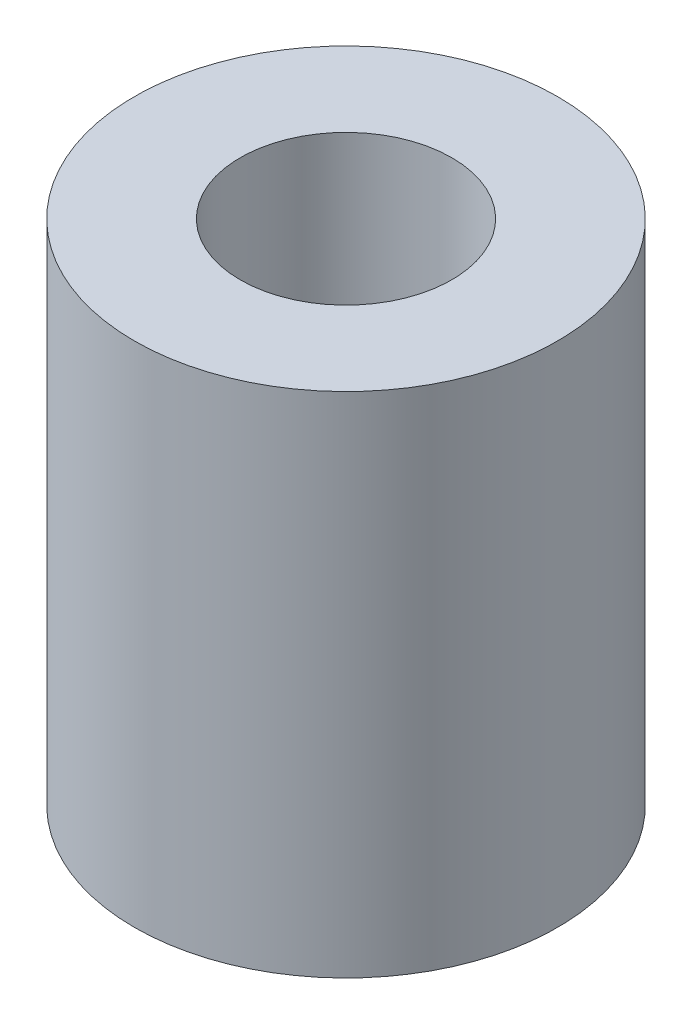
SolidWorks part; units mm, degrees
material "Brass"
ref_plane "Front Plane" through (0, 0, 0) normal (0, 0, 1) x (1, 0, 0)
ref_plane "Top Plane" through (0, 0, 0) normal (0, 1, 0) x (1, 0, 0)
ref_plane "Right Plane" through (0, 0, 0) normal (1, 0, 0) x (0, 0, -1)
sketch "Sketch1" plane through (0, 0, 0) normal (0, 1, 0) x (1, 0, 0)
  circle A0 centre (0, 0) radius 2.5
  dimension "D1" = 5
extrude "Boss-Extrude1" add sketch "Sketch1" along normal blind 6
hole_wizard "M3x0.5 Tapped Hole1" positions "Sketch2" profile "Sketch3" tap size "M3x0.5" standard "ANSI Metric" end condition through all
sketch "Sketch2" plane through (0, 6, 0) normal (0, 1, 0) x (1, 0, 0)
  point P0 (0, 0)
sketch "Sketch3" plane through (0, 6, 0) normal (1, 0, 0) x (0, 0, 1)
  line L0 (0, 0) -> (0, 6)
  line L1 (0, 6) -> (1.25, 6)
  line L2 (1.25, 6) -> (1.25, 0)
  line L5 (1.25, 0) -> (0, 0)
  line L11 (0, -6.35) -> (0, 107.95) construction
  dimension "Thru Tap Drill Dia." = 2.5
  dimension "Thru Tap Drill Depth" = 6
cosmetic thread "Hole Thread1" parameters "D2"=3
